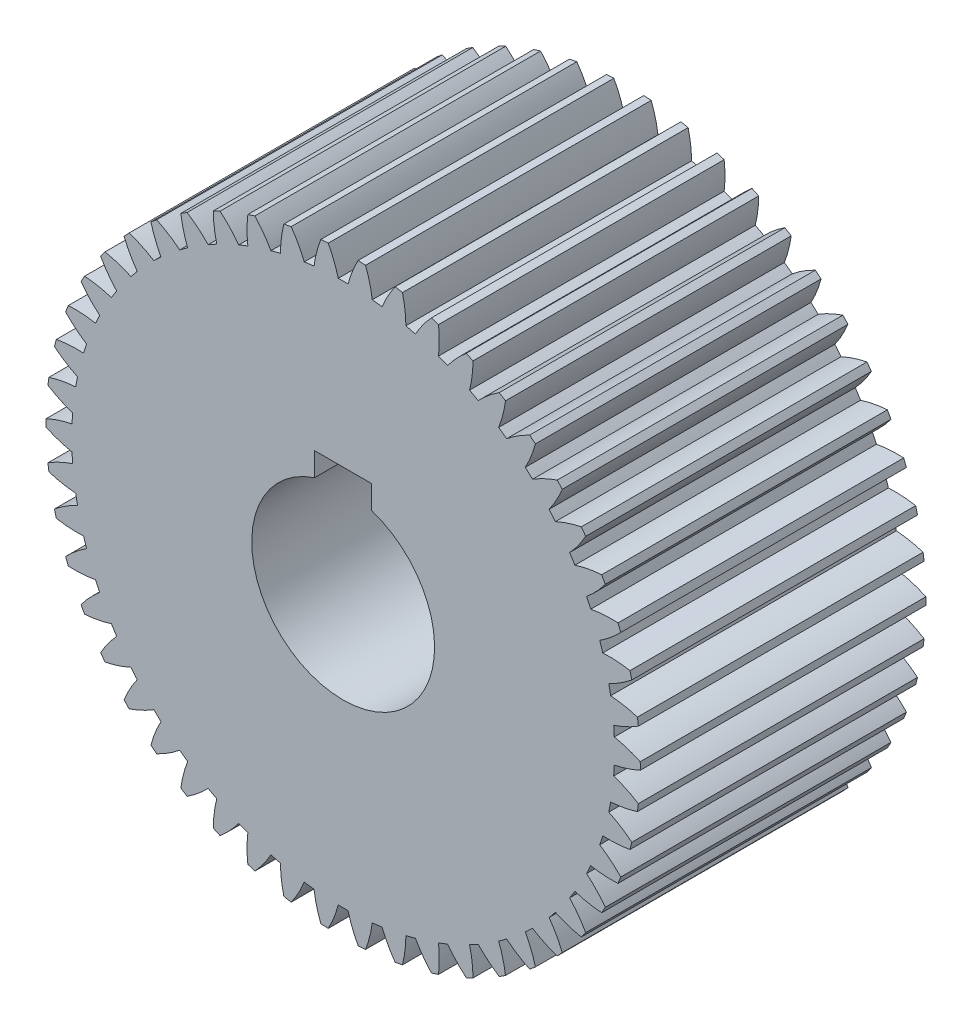
SolidWorks part; units mm, degrees
ref_plane "前视基准面" through (0, 0, 0) normal (0, 0, 1) x (1, 0, 0)
ref_plane "上视基准面" through (0, 0, 0) normal (0, 1, 0) x (1, 0, 0)
ref_plane "右视基准面" through (0, 0, 0) normal (1, 0, 0) x (0, 0, -1)
sketch "Model" plane through (0, 0, 0) normal (0, 0, 1) x (1, 0, 0)
  line L0 (5, 15.1987) -> (5, 19.3)
  line L1 (-5, 19.3) -> (-5, 15.1987)
  line L2 (5, 19.3) -> (-5, 19.3)
  arc A0 (-51.9959, -0.6505) -> (-47.4515, -2.1231) centre (-43.6027, 17.5031) ccw
  arc A1 (-47.4515, -2.1231) -> (-47.3435, -3.8409) centre (0, 0) ccw
  arc A2 (-47.3435, -3.8409) -> (-51.6675, -5.8714) centre (-41.0652, -22.83) ccw
  arc A3 (-51.6675, -5.8714) -> (-51.5044, -7.1622) centre (0, 0) ccw
  arc A4 (-51.5044, -7.1622) -> (-46.8113, -8.0536) centre (-45.4526, 11.9002) ccw
  arc A5 (-46.8113, -8.0536) -> (-46.4887, -9.7443) centre (0, 0) ccw
  arc A6 (-46.4887, -9.7443) -> (-50.5242, -12.3008) centre (-37.88, -27.7968) ccw
  arc A7 (-50.5242, -12.3008) -> (-50.2006, -13.5609) centre (0, 0) ccw
  arc A8 (-50.2006, -13.5609) -> (-45.4328, -13.8571) centre (-46.5857, 6.1097) ccw
  arc A9 (-45.4328, -13.8571) -> (-44.9009, -15.4941) centre (0, 0) ccw
  arc A10 (-44.9009, -15.4941) -> (-48.5841, -18.5361) centre (-34.0975, -32.3252) ccw
  arc A11 (-48.5841, -18.5361) -> (-48.1051, -19.7458) centre (0, 0) ccw
  arc A12 (-48.1051, -19.7458) -> (-43.3378, -19.4421) centre (-46.9841, 0.2227) ccw
  arc A13 (-43.3378, -19.4421) -> (-42.6049, -20.9995) centre (0, 0) ccw
  arc A14 (-42.6049, -20.9995) -> (-45.8778, -24.4792) centre (-29.7772, -36.3439) ccw
  arc A15 (-45.8778, -24.4792) -> (-45.251, -25.6193) centre (0, 0) ccw
  arc A16 (-45.251, -25.6193) -> (-40.5593, -24.7204) centre (-46.6415, -5.6677) ccw
  arc A17 (-40.5593, -24.7204) -> (-39.637, -26.1737) centre (0, 0) ccw
  arc A18 (-39.637, -26.1737) -> (-42.448, -30.0362) centre (-24.9873, -39.7893) ccw
  arc A19 (-42.448, -30.0362) -> (-41.6832, -31.0887) centre (0, 0) ccw
  arc A20 (-41.6832, -31.0887) -> (-37.1412, -29.6089) centre (-45.5634, -11.4687) ccw
  arc A21 (-37.1412, -29.6089) -> (-36.044, -30.9352) centre (0, 0) ccw
  arc A22 (-36.044, -30.9352) -> (-38.3487, -35.1195) centre (-19.8033, -42.6073) ccw
  arc A23 (-38.3487, -35.1195) -> (-37.4581, -36.0679) centre (0, 0) ccw
  arc A24 (-37.4581, -36.0679) -> (-33.1373, -34.0305) centre (-43.7667, -17.0889) ccw
  arc A25 (-33.1373, -34.0305) -> (-31.8826, -35.2087) centre (0, 0) ccw
  arc A26 (-31.8826, -35.2087) -> (-33.6447, -39.6489) centre (-14.307, -44.7534) ccw
  arc A27 (-33.6447, -39.6489) -> (-32.6422, -40.4782) centre (0, 0) ccw
  arc A28 (-32.6422, -40.4782) -> (-28.6109, -37.9153) centre (-41.2798, -22.4396) ccw
  arc A29 (-28.6109, -37.9153) -> (-27.2184, -38.9271) centre (0, 0) ccw
  arc A30 (-27.2184, -38.9271) -> (-28.4101, -43.553) centre (-8.5851, -46.1936) ccw
  arc A31 (-28.4101, -43.553) -> (-27.3116, -44.2502) centre (0, 0) ccw
  arc A32 (-27.3116, -44.2502) -> (-23.6332, -41.2023) centre (-38.1419, -27.4364) ccw
  arc A33 (-23.6332, -41.2023) -> (-22.1249, -42.0315) centre (0, 0) ccw
  arc A34 (-22.1249, -42.0315) -> (-22.7274, -46.7703) centre (-2.7279, -46.9054) ccw
  arc A35 (-22.7274, -46.7703) -> (-21.5502, -47.3243) centre (0, 0) ccw
  arc A36 (-21.5502, -47.3243) -> (-18.2829, -43.8394) centre (-34.4024, -32.0005) ccw
  arc A37 (-18.2829, -43.8394) -> (-16.6825, -44.473) centre (0, 0) ccw
  arc A38 (-16.6825, -44.473) -> (-16.6863, -49.25) centre (3.1725, -46.8774) ccw
  arc A39 (-16.6863, -49.25) -> (-15.4489, -49.6521) centre (0, 0) ccw
  arc A40 (-15.4489, -49.6521) -> (-12.6442, -45.7852) centre (-30.1204, -36.0599) ccw
  arc A41 (-12.6442, -45.7852) -> (-10.977, -46.2132) centre (0, 0) ccw
  arc A42 (-10.977, -46.2132) -> (-10.3821, -50.953) centre (9.0227, -46.1101) ccw
  arc A43 (-10.3821, -50.953) -> (-9.1041, -51.1968) centre (0, 0) ccw
  arc A44 (-9.1041, -51.1968) -> (-6.8061, -47.0089) centre (-25.3634, -39.5506) ccw
  arc A45 (-6.8061, -47.0089) -> (-5.0984, -47.2246) centre (0, 0) ccw
  arc A46 (-5.0984, -47.2246) -> (-3.9141, -51.8525) centre (14.7307, -44.6157) ccw
  arc A47 (-3.9141, -51.8525) -> (-2.6156, -51.9342) centre (0, 0) ccw
  arc A48 (-2.6156, -51.9342) -> (-0.8606, -47.4912) centre (-20.2064, -42.4176) ccw
  arc A49 (-0.8606, -47.4912) -> (0.8606, -47.4912) centre (0, 0) ccw
  arc A50 (0.8606, -47.4912) -> (2.6156, -51.9342) centre (20.2064, -42.4176) ccw
  arc A51 (2.6156, -51.9342) -> (3.9141, -51.8525) centre (0, 0) ccw
  arc A52 (3.9141, -51.8525) -> (5.0984, -47.2246) centre (-14.7307, -44.6157) ccw
  arc A53 (5.0984, -47.2246) -> (6.8061, -47.0089) centre (0, 0) ccw
  arc A54 (6.8061, -47.0089) -> (9.1041, -51.1968) centre (25.3634, -39.5506) ccw
  arc A55 (9.1041, -51.1968) -> (10.3821, -50.953) centre (0, 0) ccw
  arc A56 (10.3821, -50.953) -> (10.977, -46.2132) centre (-9.0227, -46.1101) ccw
  arc A57 (10.977, -46.2132) -> (12.6442, -45.7852) centre (0, 0) ccw
  arc A58 (12.6442, -45.7852) -> (15.4489, -49.6521) centre (30.1204, -36.0599) ccw
  arc A59 (15.4489, -49.6521) -> (16.6863, -49.25) centre (0, 0) ccw
  arc A60 (16.6863, -49.25) -> (16.6825, -44.473) centre (-3.1725, -46.8774) ccw
  arc A61 (16.6825, -44.473) -> (18.2829, -43.8394) centre (0, 0) ccw
  arc A62 (18.2829, -43.8394) -> (21.5502, -47.3243) centre (34.4024, -32.0005) ccw
  arc A63 (21.5502, -47.3243) -> (22.7274, -46.7703) centre (0, 0) ccw
  arc A64 (22.7274, -46.7703) -> (22.1249, -42.0315) centre (2.7279, -46.9054) ccw
  arc A65 (22.1249, -42.0315) -> (23.6332, -41.2023) centre (0, 0) ccw
  arc A66 (23.6332, -41.2023) -> (27.3116, -44.2502) centre (38.1419, -27.4364) ccw
  arc A67 (27.3116, -44.2502) -> (28.4101, -43.553) centre (0, 0) ccw
  arc A68 (28.4101, -43.553) -> (27.2184, -38.9271) centre (8.5851, -46.1936) ccw
  arc A69 (27.2184, -38.9271) -> (28.6109, -37.9153) centre (0, 0) ccw
  arc A70 (28.6109, -37.9153) -> (32.6422, -40.4782) centre (41.2798, -22.4396) ccw
  arc A71 (32.6422, -40.4782) -> (33.6447, -39.6489) centre (0, 0) ccw
  arc A72 (33.6447, -39.6489) -> (31.8826, -35.2087) centre (14.307, -44.7534) ccw
  arc A73 (31.8826, -35.2087) -> (33.1373, -34.0305) centre (0, 0) ccw
  arc A74 (33.1373, -34.0305) -> (37.4581, -36.0679) centre (43.7667, -17.0889) ccw
  arc A75 (37.4581, -36.0679) -> (38.3487, -35.1195) centre (0, 0) ccw
  arc A76 (38.3487, -35.1195) -> (36.044, -30.9352) centre (19.8033, -42.6073) ccw
  arc A77 (36.044, -30.9352) -> (37.1412, -29.6089) centre (0, 0) ccw
  arc A78 (37.1412, -29.6089) -> (41.6832, -31.0887) centre (45.5634, -11.4687) ccw
  arc A79 (41.6832, -31.0887) -> (42.448, -30.0362) centre (0, 0) ccw
  arc A80 (42.448, -30.0362) -> (39.637, -26.1737) centre (24.9873, -39.7893) ccw
  arc A81 (39.637, -26.1737) -> (40.5593, -24.7204) centre (0, 0) ccw
  arc A82 (40.5593, -24.7204) -> (45.251, -25.6193) centre (46.6415, -5.6677) ccw
  arc A83 (45.251, -25.6193) -> (45.8778, -24.4792) centre (0, 0) ccw
  arc A84 (45.8778, -24.4792) -> (42.6049, -20.9995) centre (29.7772, -36.3439) ccw
  arc A85 (42.6049, -20.9995) -> (43.3378, -19.4421) centre (0, 0) ccw
  arc A86 (43.3378, -19.4421) -> (48.1051, -19.7458) centre (46.9841, 0.2227) ccw
  arc A87 (48.1051, -19.7458) -> (48.5841, -18.5361) centre (0, 0) ccw
  arc A88 (48.5841, -18.5361) -> (44.9009, -15.4941) centre (34.0975, -32.3252) ccw
  arc A89 (44.9009, -15.4941) -> (45.4328, -13.8571) centre (0, 0) ccw
  arc A90 (45.4328, -13.8571) -> (50.2006, -13.5609) centre (46.5857, 6.1097) ccw
  arc A91 (50.2006, -13.5609) -> (50.5242, -12.3008) centre (0, 0) ccw
  arc A92 (50.5242, -12.3008) -> (46.4887, -9.7443) centre (37.88, -27.7968) ccw
  arc A93 (46.4887, -9.7443) -> (46.8113, -8.0536) centre (0, 0) ccw
  arc A94 (46.8113, -8.0536) -> (51.5044, -7.1622) centre (45.4526, 11.9002) ccw
  arc A95 (51.5044, -7.1622) -> (51.6675, -5.8714) centre (0, 0) ccw
  arc A96 (51.6675, -5.8714) -> (47.3435, -3.8409) centre (41.0652, -22.83) ccw
  arc A97 (47.3435, -3.8409) -> (47.4515, -2.1231) centre (0, 0) ccw
  arc A98 (47.4515, -2.1231) -> (51.9959, -0.6505) centre (43.6027, 17.5031) ccw
  arc A99 (51.9959, -0.6505) -> (51.9959, 0.6505) centre (0, 0) ccw
  arc A100 (51.9959, 0.6505) -> (47.4515, 2.1231) centre (43.6027, -17.5031) ccw
  arc A101 (47.4515, 2.1231) -> (47.3435, 3.8409) centre (0, 0) ccw
  arc A102 (47.3435, 3.8409) -> (51.6675, 5.8714) centre (41.0652, 22.83) ccw
  arc A103 (51.6675, 5.8714) -> (51.5044, 7.1622) centre (0, 0) ccw
  arc A104 (51.5044, 7.1622) -> (46.8113, 8.0536) centre (45.4526, -11.9002) ccw
  arc A105 (46.8113, 8.0536) -> (46.4887, 9.7443) centre (0, 0) ccw
  arc A106 (46.4887, 9.7443) -> (50.5242, 12.3008) centre (37.88, 27.7968) ccw
  arc A107 (50.5242, 12.3008) -> (50.2006, 13.5609) centre (0, 0) ccw
  arc A108 (50.2006, 13.5609) -> (45.4328, 13.8571) centre (46.5857, -6.1097) ccw
  arc A109 (45.4328, 13.8571) -> (44.9009, 15.4941) centre (0, 0) ccw
  arc A110 (44.9009, 15.4941) -> (48.5841, 18.5361) centre (34.0975, 32.3252) ccw
  arc A111 (48.5841, 18.5361) -> (48.1051, 19.7458) centre (0, 0) ccw
  arc A112 (48.1051, 19.7458) -> (43.3378, 19.4421) centre (46.9841, -0.2227) ccw
  arc A113 (43.3378, 19.4421) -> (42.6049, 20.9995) centre (0, 0) ccw
  arc A114 (42.6049, 20.9995) -> (45.8778, 24.4792) centre (29.7772, 36.3439) ccw
  arc A115 (45.8778, 24.4792) -> (45.251, 25.6193) centre (0, 0) ccw
  arc A116 (45.251, 25.6193) -> (40.5593, 24.7204) centre (46.6415, 5.6677) ccw
  arc A117 (40.5593, 24.7204) -> (39.637, 26.1737) centre (0, 0) ccw
  arc A118 (39.637, 26.1737) -> (42.448, 30.0362) centre (24.9873, 39.7893) ccw
  arc A119 (42.448, 30.0362) -> (41.6832, 31.0887) centre (0, 0) ccw
  arc A120 (41.6832, 31.0887) -> (37.1412, 29.6089) centre (45.5634, 11.4687) ccw
  arc A121 (37.1412, 29.6089) -> (36.044, 30.9352) centre (0, 0) ccw
  arc A122 (36.044, 30.9352) -> (38.3487, 35.1195) centre (19.8033, 42.6073) ccw
  arc A123 (38.3487, 35.1195) -> (37.4581, 36.0679) centre (0, 0) ccw
  arc A124 (37.4581, 36.0679) -> (33.1373, 34.0305) centre (43.7667, 17.0889) ccw
  arc A125 (33.1373, 34.0305) -> (31.8826, 35.2087) centre (0, 0) ccw
  arc A126 (31.8826, 35.2087) -> (33.6447, 39.6489) centre (14.307, 44.7534) ccw
  arc A127 (33.6447, 39.6489) -> (32.6422, 40.4782) centre (0, 0) ccw
  arc A128 (32.6422, 40.4782) -> (28.6109, 37.9153) centre (41.2798, 22.4396) ccw
  arc A129 (28.6109, 37.9153) -> (27.2184, 38.9271) centre (0, 0) ccw
  arc A130 (27.2184, 38.9271) -> (28.4101, 43.553) centre (8.5851, 46.1936) ccw
  arc A131 (28.4101, 43.553) -> (27.3116, 44.2502) centre (0, 0) ccw
  arc A132 (27.3116, 44.2502) -> (23.6332, 41.2023) centre (38.1419, 27.4364) ccw
  arc A133 (23.6332, 41.2023) -> (22.1249, 42.0315) centre (0, 0) ccw
  arc A134 (22.1249, 42.0315) -> (22.7274, 46.7703) centre (2.7279, 46.9054) ccw
  arc A135 (22.7274, 46.7703) -> (21.5502, 47.3243) centre (0, 0) ccw
  arc A136 (21.5502, 47.3243) -> (18.2829, 43.8394) centre (34.4024, 32.0005) ccw
  arc A137 (18.2829, 43.8394) -> (16.6825, 44.473) centre (0, 0) ccw
  arc A138 (16.6825, 44.473) -> (16.6863, 49.25) centre (-3.1725, 46.8774) ccw
  arc A139 (16.6863, 49.25) -> (15.4489, 49.6521) centre (0, 0) ccw
  arc A140 (15.4489, 49.6521) -> (12.6442, 45.7852) centre (30.1204, 36.0599) ccw
  arc A141 (12.6442, 45.7852) -> (10.977, 46.2132) centre (0, 0) ccw
  arc A142 (10.977, 46.2132) -> (10.3821, 50.953) centre (-9.0227, 46.1101) ccw
  arc A143 (10.3821, 50.953) -> (9.1041, 51.1968) centre (0, 0) ccw
  arc A144 (9.1041, 51.1968) -> (6.8061, 47.0089) centre (25.3634, 39.5506) ccw
  arc A145 (6.8061, 47.0089) -> (5.0984, 47.2246) centre (0, 0) ccw
  arc A146 (5.0984, 47.2246) -> (3.9141, 51.8525) centre (-14.7307, 44.6157) ccw
  arc A147 (3.9141, 51.8525) -> (2.6156, 51.9342) centre (0, 0) ccw
  arc A148 (2.6156, 51.9342) -> (0.8606, 47.4912) centre (20.2064, 42.4176) ccw
  arc A149 (0.8606, 47.4912) -> (-0.8606, 47.4912) centre (0, 0) ccw
  arc A150 (-0.8606, 47.4912) -> (-2.6156, 51.9342) centre (-20.2064, 42.4176) ccw
  arc A151 (-2.6156, 51.9342) -> (-3.9141, 51.8525) centre (0, 0) ccw
  arc A152 (-3.9141, 51.8525) -> (-5.0984, 47.2246) centre (14.7307, 44.6157) ccw
  arc A153 (-5.0984, 47.2246) -> (-6.8061, 47.0089) centre (0, 0) ccw
  arc A154 (-6.8061, 47.0089) -> (-9.1041, 51.1968) centre (-25.3634, 39.5506) ccw
  arc A155 (-9.1041, 51.1968) -> (-10.3821, 50.953) centre (0, 0) ccw
  arc A156 (-10.3821, 50.953) -> (-10.977, 46.2132) centre (9.0227, 46.1101) ccw
  arc A157 (-10.977, 46.2132) -> (-12.6442, 45.7852) centre (0, 0) ccw
  arc A158 (-12.6442, 45.7852) -> (-15.4489, 49.6521) centre (-30.1204, 36.0599) ccw
  arc A159 (-15.4489, 49.6521) -> (-16.6863, 49.25) centre (0, 0) ccw
  arc A160 (-16.6863, 49.25) -> (-16.6825, 44.473) centre (3.1725, 46.8774) ccw
  arc A161 (-16.6825, 44.473) -> (-18.2829, 43.8394) centre (0, 0) ccw
  arc A162 (-18.2829, 43.8394) -> (-21.5502, 47.3243) centre (-34.4024, 32.0005) ccw
  arc A163 (-21.5502, 47.3243) -> (-22.7274, 46.7703) centre (0, 0) ccw
  arc A164 (-22.7274, 46.7703) -> (-22.1249, 42.0315) centre (-2.7279, 46.9054) ccw
  arc A165 (-22.1249, 42.0315) -> (-23.6332, 41.2023) centre (0, 0) ccw
  arc A166 (-23.6332, 41.2023) -> (-27.3116, 44.2502) centre (-38.1419, 27.4364) ccw
  arc A167 (-27.3116, 44.2502) -> (-28.4101, 43.553) centre (0, 0) ccw
  arc A168 (-28.4101, 43.553) -> (-27.2184, 38.9271) centre (-8.5851, 46.1936) ccw
  arc A169 (-27.2184, 38.9271) -> (-28.6109, 37.9153) centre (0, 0) ccw
  arc A170 (-28.6109, 37.9153) -> (-32.6422, 40.4782) centre (-41.2798, 22.4396) ccw
  arc A171 (-32.6422, 40.4782) -> (-33.6447, 39.6489) centre (0, 0) ccw
  arc A172 (-33.6447, 39.6489) -> (-31.8826, 35.2087) centre (-14.307, 44.7534) ccw
  arc A173 (-31.8826, 35.2087) -> (-33.1373, 34.0305) centre (0, 0) ccw
  arc A174 (-33.1373, 34.0305) -> (-37.4581, 36.0679) centre (-43.7667, 17.0889) ccw
  arc A175 (-37.4581, 36.0679) -> (-38.3487, 35.1195) centre (0, 0) ccw
  arc A176 (-38.3487, 35.1195) -> (-36.044, 30.9352) centre (-19.8033, 42.6073) ccw
  arc A177 (-36.044, 30.9352) -> (-37.1412, 29.6089) centre (0, 0) ccw
  arc A178 (-37.1412, 29.6089) -> (-41.6832, 31.0887) centre (-45.5634, 11.4687) ccw
  arc A179 (-41.6832, 31.0887) -> (-42.448, 30.0362) centre (0, 0) ccw
  arc A180 (-42.448, 30.0362) -> (-39.637, 26.1737) centre (-24.9873, 39.7893) ccw
  arc A181 (-39.637, 26.1737) -> (-40.5593, 24.7204) centre (0, 0) ccw
  arc A182 (-40.5593, 24.7204) -> (-45.251, 25.6193) centre (-46.6415, 5.6677) ccw
  arc A183 (-45.251, 25.6193) -> (-45.8778, 24.4792) centre (0, 0) ccw
  arc A184 (-45.8778, 24.4792) -> (-42.6049, 20.9995) centre (-29.7772, 36.3439) ccw
  arc A185 (-42.6049, 20.9995) -> (-43.3378, 19.4421) centre (0, 0) ccw
  arc A186 (-43.3378, 19.4421) -> (-48.1051, 19.7458) centre (-46.9841, -0.2227) ccw
  arc A187 (-48.1051, 19.7458) -> (-48.5841, 18.5361) centre (0, 0) ccw
  arc A188 (-48.5841, 18.5361) -> (-44.9009, 15.4941) centre (-34.0975, 32.3252) ccw
  arc A189 (-44.9009, 15.4941) -> (-45.4328, 13.8571) centre (0, 0) ccw
  arc A190 (-45.4328, 13.8571) -> (-50.2006, 13.5609) centre (-46.5857, -6.1097) ccw
  arc A191 (-50.2006, 13.5609) -> (-50.5242, 12.3008) centre (0, 0) ccw
  arc A192 (-50.5242, 12.3008) -> (-46.4887, 9.7443) centre (-37.88, 27.7968) ccw
  arc A193 (-46.4887, 9.7443) -> (-46.8113, 8.0536) centre (0, 0) ccw
  arc A194 (-46.8113, 8.0536) -> (-51.5044, 7.1622) centre (-45.4526, -11.9002) ccw
  arc A195 (-51.5044, 7.1622) -> (-51.6675, 5.8714) centre (0, 0) ccw
  arc A196 (-51.6675, 5.8714) -> (-47.3435, 3.8409) centre (-41.0652, 22.83) ccw
  arc A197 (-47.3435, 3.8409) -> (-47.4515, 2.1231) centre (0, 0) ccw
  arc A198 (-47.4515, 2.1231) -> (-51.9959, 0.6505) centre (-43.6027, -17.5031) ccw
  arc A199 (-51.9959, 0.6505) -> (-51.9959, -0.6505) centre (0, 0) ccw
  arc A200 (-5, 15.1987) -> (5, 15.1987) centre (0, 0) ccw
extrude "凸台-拉伸1" add sketch "Model" along normal blind 50
